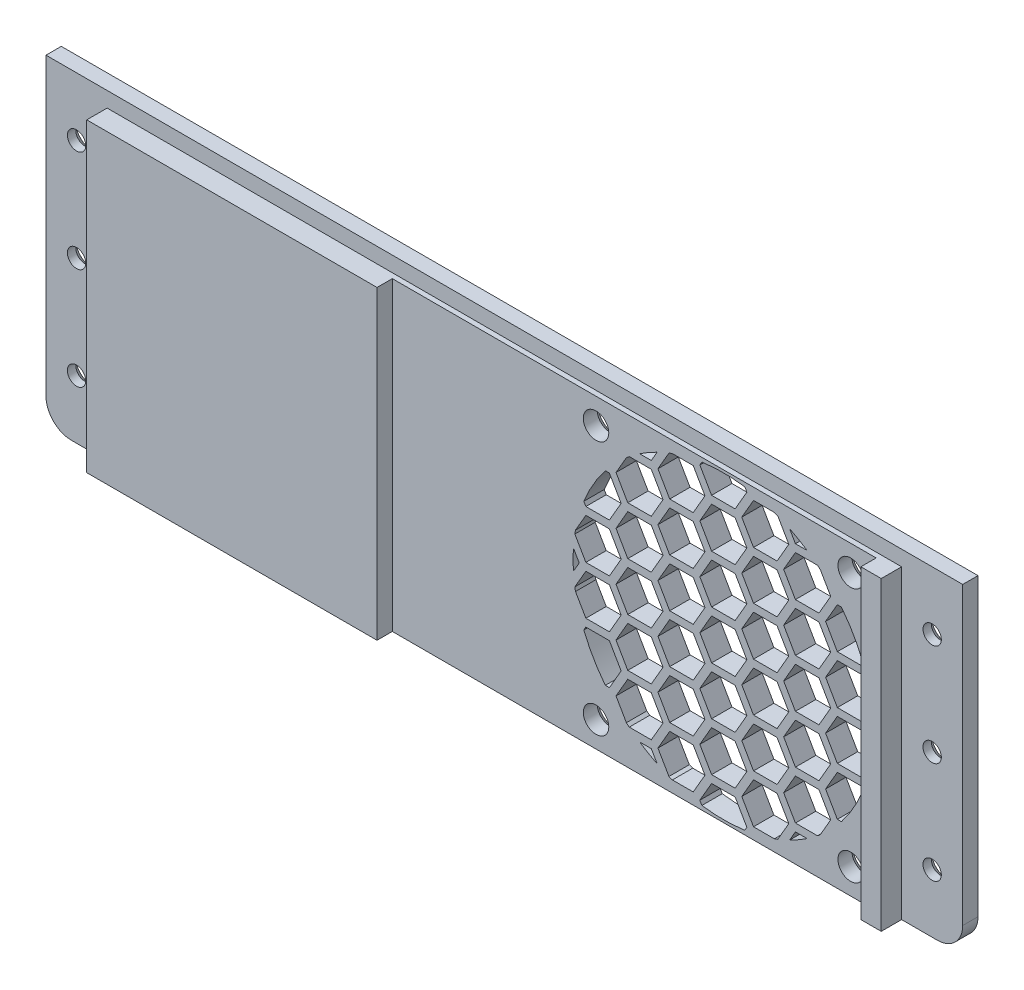
SolidWorks part; units mm, degrees
ref_plane "Front Plane" through (0, 0, 0) normal (0, 0, 1) x (1, 0, 0)
ref_plane "Top Plane" through (0, 0, 0) normal (0, 1, 0) x (1, 0, 0)
ref_plane "Right Plane" through (0, 0, 0) normal (1, 0, 0) x (0, 0, -1)
sketch "Sketch1" plane through (0, 0, 0) normal (0, 0, 1) x (1, 0, 0)
  line L1 (-90, -31.5) -> (90, -31.5)
  line L2 (-90, -31.5) -> (-90, 31.5)
  line L3 (-90, 31.5) -> (90, 31.5)
  line L4 (90, -31.5) -> (90, 31.5)
  line L5 (-90, -31.5) -> (90, 31.5) construction
  line L6 (-90, 31.5) -> (90, -31.5) construction
  point P0 (0, 0)
  dimension "D1" = 180
  dimension "D2" = 63
extrude "Boss-Extrude1" add sketch "Sketch1" along normal blind 3
fillet "Fillet1" radius 5 2 edges at (-90, -31.5, 1.5) (90, -31.5, 1.5)
sketch "Sketch2" plane through (0, 0, 3) normal (0, 0, 1) x (1, 0, 0)
  line L0 (-85, -31.5) -> (85, -31.5) construction
  line L1 (-78, -31.5) -> (78, -31.5)
  line L2 (-78, -31.5) -> (-78, 31.5)
  line L3 (-78, 31.5) -> (78, 31.5)
  line L4 (78, -31.5) -> (78, 31.5)
  line L5 (90, 31.5) -> (-90, 31.5) construction
  dimension "D1" = 12
  dimension "D2" = 12
extrude "Boss-Extrude2" add sketch "Sketch2" along normal blind 4
sketch "Sketch3" plane through (0, 0, 0) normal (0, 0, -1) x (-1, 0, 0)
  line L0 (-90, -26.5) -> (-90, 31.5) construction
  line L2 (90, -26.5) -> (90, 31.5) construction
  point P0 (-84, 20)
  point P2 (-84, -20)
  point P4 (84, 20)
  point P6 (84, -20)
  point P8 (-84, 0)
  point P10 (84, 0)
  dimension "D1" = 6
  dimension "D2" = 20
  dimension "D3" = 20
  dimension "D4" = 6
  dimension "D5" = 20
  dimension "D6" = 20
hole_wizard "CSK for M3 Flat Head Machine Screw1" positions "Sketch3" profile "Sketch4" countersink size "M3" standard "ANSI Metric"
sketch "Sketch4" plane through (84, 20, 0) normal (1, 0, 0) x (0, 1, 0)
  line L0 (0, 0) -> (0, 9.0815)
  line L1 (0, 9.0815) -> (1.8, 8)
  line L2 (1.8, 8) -> (1.8, 1.35)
  line L3 (1.8, 1.35) -> (3.15, 0)
  line L5 (3.15, 0) -> (0, 0)
  line L6 (-1.8, 1.35) -> (-3.15, 0) construction
  line L10 (0, 9.0815) -> (-1.8, 8) construction
  line L11 (0, -6.35) -> (0, 107.95) construction
  dimension "Hole Dia." = 3.6
  dimension "Hole Depth" = 8
  dimension "Near C'Sink Dia." = 6.3
  dimension "Near C'Sink Angle" = 90
  dimension "Drill Angle" = 118
sketch "Sketch9" plane through (0, 0, 7) normal (0, 0, 1) x (1, 0, 0)
  line L0 (-78, -31.5) -> (78, -31.5) construction
  line L1 (14, -31.5) -> (74, -31.5)
  line L2 (14, -31.5) -> (14, 28.5)
  line L3 (14, 28.5) -> (74, 28.5)
  line L4 (74, -31.5) -> (74, 28.5)
  line L5 (14, -31.5) -> (74, 28.5) construction
  line L6 (14, 28.5) -> (74, -31.5) construction
  line L11 (78, -31.5) -> (78, 31.5) construction
  line L13 (69, -26.5) -> (19, -26.5)
  line L14 (69, -26.5) -> (69, 23.5)
  line L15 (69, 23.5) -> (19, 23.5)
  line L16 (19, -26.5) -> (19, 23.5)
  line L17 (69, -26.5) -> (19, 23.5) construction
  line L18 (69, 23.5) -> (19, -26.5) construction
  point P0 (44, -1.5)
  point P10 (44, -1.5)
  dimension "D1" = 60
  dimension "D2" = 60
  dimension "D3" = 4
  dimension "D4" = 50
sketch "Sketch12" plane through (0, 0, 0) normal (0, 0, -1) x (-1, 0, 0)
  point P0 (-19, 23.5)
  point P2 (-19, -26.5)
  point P4 (-69, -26.5)
  point P6 (-69, 23.5)
hole_wizard "CSK for M3 Flat Head Machine Screw3" positions "Sketch12" profile "Sketch14" countersink size "M3" standard "ANSI Metric" end condition through all
sketch "Sketch14" plane through (19, 23.5, 0) normal (1, 0, 0) x (0, 1, 0)
  line L0 (0, 0) -> (0, 7)
  line L1 (0, 7) -> (2.5, 7)
  line L2 (2.5, 7) -> (2.5, 1.25)
  line L3 (2.5, 1.25) -> (3.75, 0)
  line L5 (3.75, 0) -> (0, 0)
  line L6 (-2.5, 1.25) -> (-3.75, 0) construction
  line L11 (0, -6.35) -> (0, 107.95) construction
  dimension "Thru Hole Dia." = 5
  dimension "Thru Hole Depth" = 7
  dimension "Near C'Sink Dia." = 7.5
  dimension "Near C'Sink Angle" = 90
sketch "Sketch15" plane through (0, 0, 7) normal (0, 0, 1) x (1, 0, 0)
  line L0 (-78, -31.5) -> (78, -31.5) construction
  line L1 (74, -31.5) -> (-21, -31.5)
  line L2 (74, -31.5) -> (74, 31.5)
  line L3 (74, 31.5) -> (-21, 31.5)
  line L4 (-21, -31.5) -> (-21, 31.5)
  line L5 (78, 31.5) -> (-78, 31.5) construction
  line L6 (78, -31.5) -> (78, 31.5) construction
  dimension "D1" = 4
  dimension "D2" = 95
extrude "Cut-Extrude3" cut sketch "Sketch15" against normal blind 3
sketch "Sketch16" plane through (0, 0, 0) normal (0, 0, -1) x (-1, 0, 0)
  circle A4 centre (-64, 13.5) radius 3.75
  circle A53 centre (-69, 23.5) radius 3.75 construction
  circle A54 centre (-69, 23.5) radius 3.75
  circle A55 centre (-19, 23.5) radius 3.75 construction
  circle A56 centre (-19, 23.5) radius 3.75
  circle A57 centre (-59, 23.5) radius 3.75
  circle A58 centre (-49, 23.5) radius 3.75
  circle A59 centre (-39, 23.5) radius 3.75
  circle A60 centre (-29, 23.5) radius 3.75
  circle A61 centre (-54, 13.5) radius 3.75
  circle A62 centre (-44, 13.5) radius 3.75
  circle A63 centre (-34, 13.5) radius 3.75
  circle A64 centre (-24, 13.5) radius 3.75
  circle A65 centre (-14, 13.5) radius 3.75
  circle A66 centre (-4, 13.5) radius 3.75
  circle A67 centre (6, 13.5) radius 3.75
  circle A68 centre (-54, -6.5) radius 3.75
  circle A69 centre (-44, -6.5) radius 3.75
  circle A70 centre (-34, -6.5) radius 3.75
  circle A71 centre (-24, -6.5) radius 3.75
  circle A72 centre (-14, -6.5) radius 3.75
  circle A73 centre (-4, -6.5) radius 3.75
  circle A74 centre (6, -6.5) radius 3.75
  circle A75 centre (-64, -6.5) radius 3.75
  circle A76 centre (-59, 23.5) radius 3.75
  circle A77 centre (-49, 23.5) radius 3.75
  circle A78 centre (-39, 23.5) radius 3.75
  circle A79 centre (-29, 23.5) radius 3.75
  circle A80 centre (-19, 23.5) radius 3.75
  circle A81 centre (-9, 23.5) radius 3.75
  circle A82 centre (1, 23.5) radius 3.75
  circle A83 centre (-59, 3.5) radius 3.75
  circle A84 centre (-49, 3.5) radius 3.75
  circle A85 centre (-39, 3.5) radius 3.75
  circle A86 centre (-29, 3.5) radius 3.75
  circle A87 centre (-19, 3.5) radius 3.75
  circle A88 centre (-9, 3.5) radius 3.75
  circle A89 centre (1, 3.5) radius 3.75
  circle A90 centre (-59, -16.5) radius 3.75
  circle A91 centre (-49, -16.5) radius 3.75
  circle A92 centre (-39, -16.5) radius 3.75
  circle A93 centre (-29, -16.5) radius 3.75
  circle A94 centre (-19, -16.5) radius 3.75
  circle A95 centre (-9, -16.5) radius 3.75
  circle A96 centre (1, -16.5) radius 3.75
  circle A97 centre (-69, 3.5) radius 3.75
  circle A98 centre (-69, -16.5) radius 3.75
  dimension "D1" = 5
  dimension "D2" = 10
  dimension "D3" = 5
sketch "Sketch17" plane through (0, 0, 0) normal (0, 0, -1) x (-1, 0, 0)
  circle A0 centre (-44, -1.5) radius 29.5
  dimension "D1" = 59
extrude "Cut-Extrude7" cut sketch "Sketch17" against normal through all
sketch "Sketch18" plane through (0, 31.5, 0) normal (0, 1, 0) x (1, 0, 0)
  line L1 (-90, -3) -> (90, -3)
  line L2 (-90, -3) -> (-90, -11)
  line L3 (-90, -11) -> (90, -11)
  line L4 (90, -3) -> (90, -11)
  dimension "D1" = 8
extrude "Cut-Extrude8" cut sketch "Sketch18" against normal blind 3
sketch "Sketch20" plane through (0, 0, 0) normal (0, 0, -1) x (-1, 0, 0)
  line L0 (-90, -26.5) -> (-90, 31.5) construction
  line L1 (-10, 28) -> (20, 28)
  line L2 (-10, 28) -> (-10, -31)
  line L3 (-10, -31) -> (20, -31)
  line L4 (20, 28) -> (20, -31)
  line L5 (-10, 28) -> (20, -31) construction
  line L6 (-10, -31) -> (20, 28) construction
  circle A0 centre (-44, -1.5) radius 29.5 construction
  point P0 (5, -1.5)
  dimension "D1" = 30
  dimension "D2" = 95
extrude "Cut-Extrude9" cut sketch "Sketch20" against normal through all
sketch "Sketch19" plane through (0, 0, 0) normal (0, 0, -1) x (-1, 0, 0)
  line L0 (-44, -1.5) -> (-35.7728, 3.25) construction
  line L1 (-39.3812, -1.5) -> (-41.6906, 2.5)
  line L2 (-41.6906, 2.5) -> (-46.3094, 2.5)
  line L3 (-46.3094, 2.5) -> (-48.6188, -1.5)
  line L4 (-48.6188, -1.5) -> (-46.3094, -5.5)
  line L5 (-46.3094, -5.5) -> (-41.6906, -5.5)
  line L6 (-41.6906, -5.5) -> (-39.3812, -1.5)
  line L7 (-31.154, 3.25) -> (-33.4634, 7.25)
  line L8 (-33.4634, 7.25) -> (-38.0822, 7.25)
  line L9 (-38.0822, 7.25) -> (-40.3916, 3.25)
  line L10 (-40.3916, 3.25) -> (-38.0822, -0.75)
  line L11 (-38.0822, -0.75) -> (-33.4634, -0.75)
  line L12 (-33.4634, -0.75) -> (-31.154, 3.25)
  line L13 (-44, -1.5) -> (-35.7728, -1.5) construction
  line L14 (-39.3812, -11) -> (-41.6906, -7)
  line L15 (-41.6906, -7) -> (-46.3094, -7)
  line L16 (-46.3094, -7) -> (-48.6188, -11)
  line L17 (-48.6188, -11) -> (-46.3094, -15)
  line L18 (-46.3094, -15) -> (-41.6906, -15)
  line L19 (-41.6906, -15) -> (-39.3812, -11)
  line L20 (-31.154, -6.25) -> (-33.4634, -2.25)
  line L21 (-33.4634, -2.25) -> (-38.0822, -2.25)
  line L22 (-38.0822, -2.25) -> (-40.3916, -6.25)
  line L23 (-40.3916, -6.25) -> (-38.0822, -10.25)
  line L24 (-38.0822, -10.25) -> (-33.4634, -10.25)
  line L25 (-33.4634, -10.25) -> (-31.154, -6.25)
  line L26 (-22.9212, -1.5) -> (-25.2306, 2.5)
  line L27 (-25.2306, 2.5) -> (-29.8494, 2.5)
  line L28 (-29.8494, 2.5) -> (-32.1588, -1.5)
  line L29 (-32.1588, -1.5) -> (-29.8494, -5.5)
  line L30 (-29.8494, -5.5) -> (-25.2306, -5.5)
  line L31 (-25.2306, -5.5) -> (-22.9212, -1.5)
  line L32 (-6.4612, -1.5) -> (-8.7706, 2.5)
  line L33 (-8.7706, 2.5) -> (-13.3894, 2.5)
  line L34 (-13.3894, 2.5) -> (-15.6988, -1.5)
  line L35 (-15.6988, -1.5) -> (-13.3894, -5.5)
  line L36 (-13.3894, -5.5) -> (-8.7706, -5.5)
  line L37 (-8.7706, -5.5) -> (-6.4612, -1.5)
  line L38 (-22.9212, -11) -> (-25.2306, -7)
  line L39 (-25.2306, -7) -> (-29.8494, -7)
  line L40 (-29.8494, -7) -> (-32.1588, -11)
  line L41 (-32.1588, -11) -> (-29.8494, -15)
  line L42 (-29.8494, -15) -> (-25.2306, -15)
  line L43 (-25.2306, -15) -> (-22.9212, -11)
  line L44 (-6.4612, -11) -> (-8.7706, -7)
  line L45 (-8.7706, -7) -> (-13.3894, -7)
  line L46 (-13.3894, -7) -> (-15.6988, -11)
  line L47 (-15.6988, -11) -> (-13.3894, -15)
  line L48 (-13.3894, -15) -> (-8.7706, -15)
  line L49 (-8.7706, -15) -> (-6.4612, -11)
  line L50 (-22.9212, -20.5) -> (-25.2306, -16.5)
  line L51 (-25.2306, -16.5) -> (-29.8494, -16.5)
  line L52 (-29.8494, -16.5) -> (-32.1588, -20.5)
  line L53 (-32.1588, -20.5) -> (-29.8494, -24.5)
  line L54 (-29.8494, -24.5) -> (-25.2306, -24.5)
  line L55 (-25.2306, -24.5) -> (-22.9212, -20.5)
  line L56 (-6.4612, -20.5) -> (-8.7706, -16.5)
  line L57 (-8.7706, -16.5) -> (-13.3894, -16.5)
  line L58 (-13.3894, -16.5) -> (-15.6988, -20.5)
  line L59 (-15.6988, -20.5) -> (-13.3894, -24.5)
  line L60 (-13.3894, -24.5) -> (-8.7706, -24.5)
  line L61 (-8.7706, -24.5) -> (-6.4612, -20.5)
  line L62 (-22.9212, -30) -> (-25.2306, -26)
  line L63 (-25.2306, -26) -> (-29.8494, -26)
  line L64 (-29.8494, -26) -> (-32.1588, -30)
  line L65 (-32.1588, -30) -> (-29.8494, -34)
  line L66 (-29.8494, -34) -> (-25.2306, -34)
  line L67 (-25.2306, -34) -> (-22.9212, -30)
  line L68 (-6.4612, -30) -> (-8.7706, -26)
  line L69 (-8.7706, -26) -> (-13.3894, -26)
  line L70 (-13.3894, -26) -> (-15.6988, -30)
  line L71 (-15.6988, -30) -> (-13.3894, -34)
  line L72 (-13.3894, -34) -> (-8.7706, -34)
  line L73 (-8.7706, -34) -> (-6.4612, -30)
  line L74 (-39.3812, -11) -> (-41.6906, -7)
  line L75 (-41.6906, -7) -> (-46.3094, -7)
  line L76 (-46.3094, -7) -> (-48.6188, -11)
  line L77 (-48.6188, -11) -> (-46.3094, -15)
  line L78 (-46.3094, -15) -> (-41.6906, -15)
  line L79 (-41.6906, -15) -> (-39.3812, -11)
  line L80 (-39.3812, -20.5) -> (-41.6906, -16.5)
  line L81 (-41.6906, -16.5) -> (-46.3094, -16.5)
  line L82 (-46.3094, -16.5) -> (-48.6188, -20.5)
  line L83 (-48.6188, -20.5) -> (-46.3094, -24.5)
  line L84 (-46.3094, -24.5) -> (-41.6906, -24.5)
  line L85 (-41.6906, -24.5) -> (-39.3812, -20.5)
  line L86 (-39.3812, -30) -> (-41.6906, -26)
  line L87 (-41.6906, -26) -> (-46.3094, -26)
  line L88 (-46.3094, -26) -> (-48.6188, -30)
  line L89 (-48.6188, -30) -> (-46.3094, -34)
  line L90 (-46.3094, -34) -> (-41.6906, -34)
  line L91 (-41.6906, -34) -> (-39.3812, -30)
  line L92 (-39.3812, 8) -> (-41.6906, 12)
  line L93 (-41.6906, 12) -> (-46.3094, 12)
  line L94 (-46.3094, 12) -> (-48.6188, 8)
  line L95 (-48.6188, 8) -> (-46.3094, 4)
  line L96 (-46.3094, 4) -> (-41.6906, 4)
  line L97 (-41.6906, 4) -> (-39.3812, 8)
  line L98 (-22.9212, 8) -> (-25.2306, 12)
  line L99 (-25.2306, 12) -> (-29.8494, 12)
  line L100 (-29.8494, 12) -> (-32.1588, 8)
  line L101 (-32.1588, 8) -> (-29.8494, 4)
  line L102 (-29.8494, 4) -> (-25.2306, 4)
  line L103 (-25.2306, 4) -> (-22.9212, 8)
  line L104 (-6.4612, 8) -> (-8.7706, 12)
  line L105 (-8.7706, 12) -> (-13.3894, 12)
  line L106 (-13.3894, 12) -> (-15.6988, 8)
  line L107 (-15.6988, 8) -> (-13.3894, 4)
  line L108 (-13.3894, 4) -> (-8.7706, 4)
  line L109 (-8.7706, 4) -> (-6.4612, 8)
  line L110 (-39.3812, 17.5) -> (-41.6906, 21.5)
  line L111 (-41.6906, 21.5) -> (-46.3094, 21.5)
  line L112 (-46.3094, 21.5) -> (-48.6188, 17.5)
  line L113 (-48.6188, 17.5) -> (-46.3094, 13.5)
  line L114 (-46.3094, 13.5) -> (-41.6906, 13.5)
  line L115 (-41.6906, 13.5) -> (-39.3812, 17.5)
  line L116 (-22.9212, 17.5) -> (-25.2306, 21.5)
  line L117 (-25.2306, 21.5) -> (-29.8494, 21.5)
  line L118 (-29.8494, 21.5) -> (-32.1588, 17.5)
  line L119 (-32.1588, 17.5) -> (-29.8494, 13.5)
  line L120 (-29.8494, 13.5) -> (-25.2306, 13.5)
  line L121 (-25.2306, 13.5) -> (-22.9212, 17.5)
  line L122 (-6.4612, 17.5) -> (-8.7706, 21.5)
  line L123 (-8.7706, 21.5) -> (-13.3894, 21.5)
  line L124 (-13.3894, 21.5) -> (-15.6988, 17.5)
  line L125 (-15.6988, 17.5) -> (-13.3894, 13.5)
  line L126 (-13.3894, 13.5) -> (-8.7706, 13.5)
  line L127 (-8.7706, 13.5) -> (-6.4612, 17.5)
  line L128 (-39.3812, 27) -> (-41.6906, 31)
  line L129 (-41.6906, 31) -> (-46.3094, 31)
  line L130 (-46.3094, 31) -> (-48.6188, 27)
  line L131 (-48.6188, 27) -> (-46.3094, 23)
  line L132 (-46.3094, 23) -> (-41.6906, 23)
  line L133 (-41.6906, 23) -> (-39.3812, 27)
  line L134 (-22.9212, 27) -> (-25.2306, 31)
  line L135 (-25.2306, 31) -> (-29.8494, 31)
  line L136 (-29.8494, 31) -> (-32.1588, 27)
  line L137 (-32.1588, 27) -> (-29.8494, 23)
  line L138 (-29.8494, 23) -> (-25.2306, 23)
  line L139 (-25.2306, 23) -> (-22.9212, 27)
  line L140 (-6.4612, 27) -> (-8.7706, 31)
  line L141 (-8.7706, 31) -> (-13.3894, 31)
  line L142 (-13.3894, 31) -> (-15.6988, 27)
  line L143 (-15.6988, 27) -> (-13.3894, 23)
  line L144 (-13.3894, 23) -> (-8.7706, 23)
  line L145 (-8.7706, 23) -> (-6.4612, 27)
  line L146 (-31.154, 12.75) -> (-33.4634, 16.75)
  line L147 (-33.4634, 16.75) -> (-38.0822, 16.75)
  line L148 (-38.0822, 16.75) -> (-40.3916, 12.75)
  line L149 (-40.3916, 12.75) -> (-38.0822, 8.75)
  line L150 (-38.0822, 8.75) -> (-33.4634, 8.75)
  line L151 (-33.4634, 8.75) -> (-31.154, 12.75)
  line L152 (-31.154, 22.25) -> (-33.4634, 26.25)
  line L153 (-33.4634, 26.25) -> (-38.0822, 26.25)
  line L154 (-38.0822, 26.25) -> (-40.3916, 22.25)
  line L155 (-40.3916, 22.25) -> (-38.0822, 18.25)
  line L156 (-38.0822, 18.25) -> (-33.4634, 18.25)
  line L157 (-33.4634, 18.25) -> (-31.154, 22.25)
  line L158 (-31.154, -15.75) -> (-33.4634, -11.75)
  line L159 (-33.4634, -11.75) -> (-38.0822, -11.75)
  line L160 (-38.0822, -11.75) -> (-40.3916, -15.75)
  line L161 (-40.3916, -15.75) -> (-38.0822, -19.75)
  line L162 (-38.0822, -19.75) -> (-33.4634, -19.75)
  line L163 (-33.4634, -19.75) -> (-31.154, -15.75)
  line L164 (-31.154, -25.25) -> (-33.4634, -21.25)
  line L165 (-33.4634, -21.25) -> (-38.0822, -21.25)
  line L166 (-38.0822, -21.25) -> (-40.3916, -25.25)
  line L167 (-40.3916, -25.25) -> (-38.0822, -29.25)
  line L168 (-38.0822, -29.25) -> (-33.4634, -29.25)
  line L169 (-33.4634, -29.25) -> (-31.154, -25.25)
  line L170 (-31.154, -34.75) -> (-33.4634, -30.75)
  line L171 (-33.4634, -30.75) -> (-38.0822, -30.75)
  line L172 (-38.0822, -30.75) -> (-40.3916, -34.75)
  line L173 (-40.3916, -34.75) -> (-38.0822, -38.75)
  line L174 (-38.0822, -38.75) -> (-33.4634, -38.75)
  line L175 (-33.4634, -38.75) -> (-31.154, -34.75)
  line L176 (-14.694, 22.25) -> (-17.0034, 26.25)
  line L177 (-17.0034, 26.25) -> (-21.6222, 26.25)
  line L178 (-21.6222, 26.25) -> (-23.9316, 22.25)
  line L179 (-23.9316, 22.25) -> (-21.6222, 18.25)
  line L180 (-21.6222, 18.25) -> (-17.0034, 18.25)
  line L181 (-17.0034, 18.25) -> (-14.694, 22.25)
  line L182 (-14.694, 12.75) -> (-17.0034, 16.75)
  line L183 (-17.0034, 16.75) -> (-21.6222, 16.75)
  line L184 (-21.6222, 16.75) -> (-23.9316, 12.75)
  line L185 (-23.9316, 12.75) -> (-21.6222, 8.75)
  line L186 (-21.6222, 8.75) -> (-17.0034, 8.75)
  line L187 (-17.0034, 8.75) -> (-14.694, 12.75)
  line L188 (-14.694, 3.25) -> (-17.0034, 7.25)
  line L189 (-17.0034, 7.25) -> (-21.6222, 7.25)
  line L190 (-21.6222, 7.25) -> (-23.9316, 3.25)
  line L191 (-23.9316, 3.25) -> (-21.6222, -0.75)
  line L192 (-21.6222, -0.75) -> (-17.0034, -0.75)
  line L193 (-17.0034, -0.75) -> (-14.694, 3.25)
  line L194 (-14.694, -6.25) -> (-17.0034, -2.25)
  line L195 (-17.0034, -2.25) -> (-21.6222, -2.25)
  line L196 (-21.6222, -2.25) -> (-23.9316, -6.25)
  line L197 (-23.9316, -6.25) -> (-21.6222, -10.25)
  line L198 (-21.6222, -10.25) -> (-17.0034, -10.25)
  line L199 (-17.0034, -10.25) -> (-14.694, -6.25)
  line L200 (-14.694, -15.75) -> (-17.0034, -11.75)
  line L201 (-17.0034, -11.75) -> (-21.6222, -11.75)
  line L202 (-21.6222, -11.75) -> (-23.9316, -15.75)
  line L203 (-23.9316, -15.75) -> (-21.6222, -19.75)
  line L204 (-21.6222, -19.75) -> (-17.0034, -19.75)
  line L205 (-17.0034, -19.75) -> (-14.694, -15.75)
  line L206 (-14.694, -25.25) -> (-17.0034, -21.25)
  line L207 (-17.0034, -21.25) -> (-21.6222, -21.25)
  line L208 (-21.6222, -21.25) -> (-23.9316, -25.25)
  line L209 (-23.9316, -25.25) -> (-21.6222, -29.25)
  line L210 (-21.6222, -29.25) -> (-17.0034, -29.25)
  line L211 (-17.0034, -29.25) -> (-14.694, -25.25)
  line L212 (-55.8412, 27) -> (-58.1506, 31)
  line L213 (-58.1506, 31) -> (-62.7694, 31)
  line L214 (-62.7694, 31) -> (-65.0788, 27)
  line L215 (-65.0788, 27) -> (-62.7694, 23)
  line L216 (-62.7694, 23) -> (-58.1506, 23)
  line L217 (-58.1506, 23) -> (-55.8412, 27)
  line L218 (-55.8412, 17.5) -> (-58.1506, 21.5)
  line L219 (-58.1506, 21.5) -> (-62.7694, 21.5)
  line L220 (-62.7694, 21.5) -> (-65.0788, 17.5)
  line L221 (-65.0788, 17.5) -> (-62.7694, 13.5)
  line L222 (-62.7694, 13.5) -> (-58.1506, 13.5)
  line L223 (-58.1506, 13.5) -> (-55.8412, 17.5)
  line L224 (-47.614, 22.25) -> (-49.9234, 26.25)
  line L225 (-49.9234, 26.25) -> (-54.5422, 26.25)
  line L226 (-54.5422, 26.25) -> (-56.8516, 22.25)
  line L227 (-56.8516, 22.25) -> (-54.5422, 18.25)
  line L228 (-54.5422, 18.25) -> (-49.9234, 18.25)
  line L229 (-49.9234, 18.25) -> (-47.614, 22.25)
  line L230 (-47.614, 12.75) -> (-49.9234, 16.75)
  line L231 (-49.9234, 16.75) -> (-54.5422, 16.75)
  line L232 (-54.5422, 16.75) -> (-56.8516, 12.75)
  line L233 (-56.8516, 12.75) -> (-54.5422, 8.75)
  line L234 (-54.5422, 8.75) -> (-49.9234, 8.75)
  line L235 (-49.9234, 8.75) -> (-47.614, 12.75)
  line L236 (-55.8412, 8) -> (-58.1506, 12)
  line L237 (-58.1506, 12) -> (-62.7694, 12)
  line L238 (-62.7694, 12) -> (-65.0788, 8)
  line L239 (-65.0788, 8) -> (-62.7694, 4)
  line L240 (-62.7694, 4) -> (-58.1506, 4)
  line L241 (-58.1506, 4) -> (-55.8412, 8)
  line L242 (-47.614, 3.25) -> (-49.9234, 7.25)
  line L243 (-49.9234, 7.25) -> (-54.5422, 7.25)
  line L244 (-54.5422, 7.25) -> (-56.8516, 3.25)
  line L245 (-56.8516, 3.25) -> (-54.5422, -0.75)
  line L246 (-54.5422, -0.75) -> (-49.9234, -0.75)
  line L247 (-49.9234, -0.75) -> (-47.614, 3.25)
  line L248 (-55.8412, -1.5) -> (-58.1506, 2.5)
  line L249 (-58.1506, 2.5) -> (-62.7694, 2.5)
  line L250 (-62.7694, 2.5) -> (-65.0788, -1.5)
  line L251 (-65.0788, -1.5) -> (-62.7694, -5.5)
  line L252 (-62.7694, -5.5) -> (-58.1506, -5.5)
  line L253 (-58.1506, -5.5) -> (-55.8412, -1.5)
  line L254 (-47.614, -6.25) -> (-49.9234, -2.25)
  line L255 (-49.9234, -2.25) -> (-54.5422, -2.25)
  line L256 (-54.5422, -2.25) -> (-56.8516, -6.25)
  line L257 (-56.8516, -6.25) -> (-54.5422, -10.25)
  line L258 (-54.5422, -10.25) -> (-49.9234, -10.25)
  line L259 (-49.9234, -10.25) -> (-47.614, -6.25)
  line L260 (-55.8412, -11) -> (-58.1506, -7)
  line L261 (-58.1506, -7) -> (-62.7694, -7)
  line L262 (-62.7694, -7) -> (-65.0788, -11)
  line L263 (-65.0788, -11) -> (-62.7694, -15)
  line L264 (-62.7694, -15) -> (-58.1506, -15)
  line L265 (-58.1506, -15) -> (-55.8412, -11)
  line L266 (-47.614, -15.75) -> (-49.9234, -11.75)
  line L267 (-49.9234, -11.75) -> (-54.5422, -11.75)
  line L268 (-54.5422, -11.75) -> (-56.8516, -15.75)
  line L269 (-56.8516, -15.75) -> (-54.5422, -19.75)
  line L270 (-54.5422, -19.75) -> (-49.9234, -19.75)
  line L271 (-49.9234, -19.75) -> (-47.614, -15.75)
  line L272 (-55.8412, -20.5) -> (-58.1506, -16.5)
  line L273 (-58.1506, -16.5) -> (-62.7694, -16.5)
  line L274 (-62.7694, -16.5) -> (-65.0788, -20.5)
  line L275 (-65.0788, -20.5) -> (-62.7694, -24.5)
  line L276 (-62.7694, -24.5) -> (-58.1506, -24.5)
  line L277 (-58.1506, -24.5) -> (-55.8412, -20.5)
  line L278 (-47.614, -25.25) -> (-49.9234, -21.25)
  line L279 (-49.9234, -21.25) -> (-54.5422, -21.25)
  line L280 (-54.5422, -21.25) -> (-56.8516, -25.25)
  line L281 (-56.8516, -25.25) -> (-54.5422, -29.25)
  line L282 (-54.5422, -29.25) -> (-49.9234, -29.25)
  line L283 (-49.9234, -29.25) -> (-47.614, -25.25)
  line L284 (-55.8412, -30) -> (-58.1506, -26)
  line L285 (-58.1506, -26) -> (-62.7694, -26)
  line L286 (-62.7694, -26) -> (-65.0788, -30)
  line L287 (-65.0788, -30) -> (-62.7694, -34)
  line L288 (-62.7694, -34) -> (-58.1506, -34)
  line L289 (-58.1506, -34) -> (-55.8412, -30)
  line L290 (-47.614, -34.75) -> (-49.9234, -30.75)
  line L291 (-49.9234, -30.75) -> (-54.5422, -30.75)
  line L292 (-54.5422, -30.75) -> (-56.8516, -34.75)
  line L293 (-56.8516, -34.75) -> (-54.5422, -38.75)
  line L294 (-54.5422, -38.75) -> (-49.9234, -38.75)
  line L295 (-49.9234, -38.75) -> (-47.614, -34.75)
  line L296 (-72.3012, 27) -> (-74.6106, 31)
  line L297 (-74.6106, 31) -> (-79.2294, 31)
  line L298 (-79.2294, 31) -> (-81.5388, 27)
  line L299 (-81.5388, 27) -> (-79.2294, 23)
  line L300 (-79.2294, 23) -> (-74.6106, 23)
  line L301 (-74.6106, 23) -> (-72.3012, 27)
  line L302 (-72.3012, 17.5) -> (-74.6106, 21.5)
  line L303 (-74.6106, 21.5) -> (-79.2294, 21.5)
  line L304 (-79.2294, 21.5) -> (-81.5388, 17.5)
  line L305 (-81.5388, 17.5) -> (-79.2294, 13.5)
  line L306 (-79.2294, 13.5) -> (-74.6106, 13.5)
  line L307 (-74.6106, 13.5) -> (-72.3012, 17.5)
  line L308 (-64.074, 22.25) -> (-66.3834, 26.25)
  line L309 (-66.3834, 26.25) -> (-71.0022, 26.25)
  line L310 (-71.0022, 26.25) -> (-73.3116, 22.25)
  line L311 (-73.3116, 22.25) -> (-71.0022, 18.25)
  line L312 (-71.0022, 18.25) -> (-66.3834, 18.25)
  line L313 (-66.3834, 18.25) -> (-64.074, 22.25)
  line L314 (-64.074, 12.75) -> (-66.3834, 16.75)
  line L315 (-66.3834, 16.75) -> (-71.0022, 16.75)
  line L316 (-71.0022, 16.75) -> (-73.3116, 12.75)
  line L317 (-73.3116, 12.75) -> (-71.0022, 8.75)
  line L318 (-71.0022, 8.75) -> (-66.3834, 8.75)
  line L319 (-66.3834, 8.75) -> (-64.074, 12.75)
  line L320 (-72.3012, 8) -> (-74.6106, 12)
  line L321 (-74.6106, 12) -> (-79.2294, 12)
  line L322 (-79.2294, 12) -> (-81.5388, 8)
  line L323 (-81.5388, 8) -> (-79.2294, 4)
  line L324 (-79.2294, 4) -> (-74.6106, 4)
  line L325 (-74.6106, 4) -> (-72.3012, 8)
  line L326 (-64.074, 3.25) -> (-66.3834, 7.25)
  line L327 (-66.3834, 7.25) -> (-71.0022, 7.25)
  line L328 (-71.0022, 7.25) -> (-73.3116, 3.25)
  line L329 (-73.3116, 3.25) -> (-71.0022, -0.75)
  line L330 (-71.0022, -0.75) -> (-66.3834, -0.75)
  line L331 (-66.3834, -0.75) -> (-64.074, 3.25)
  line L332 (-72.3012, -1.5) -> (-74.6106, 2.5)
  line L333 (-74.6106, 2.5) -> (-79.2294, 2.5)
  line L334 (-79.2294, 2.5) -> (-81.5388, -1.5)
  line L335 (-81.5388, -1.5) -> (-79.2294, -5.5)
  line L336 (-79.2294, -5.5) -> (-74.6106, -5.5)
  line L337 (-74.6106, -5.5) -> (-72.3012, -1.5)
  line L338 (-64.074, -6.25) -> (-66.3834, -2.25)
  line L339 (-66.3834, -2.25) -> (-71.0022, -2.25)
  line L340 (-71.0022, -2.25) -> (-73.3116, -6.25)
  line L341 (-73.3116, -6.25) -> (-71.0022, -10.25)
  line L342 (-71.0022, -10.25) -> (-66.3834, -10.25)
  line L343 (-66.3834, -10.25) -> (-64.074, -6.25)
  line L344 (-72.3012, -11) -> (-74.6106, -7)
  line L345 (-74.6106, -7) -> (-79.2294, -7)
  line L346 (-79.2294, -7) -> (-81.5388, -11)
  line L347 (-81.5388, -11) -> (-79.2294, -15)
  line L348 (-79.2294, -15) -> (-74.6106, -15)
  line L349 (-74.6106, -15) -> (-72.3012, -11)
  line L350 (-64.074, -15.75) -> (-66.3834, -11.75)
  line L351 (-66.3834, -11.75) -> (-71.0022, -11.75)
  line L352 (-71.0022, -11.75) -> (-73.3116, -15.75)
  line L353 (-73.3116, -15.75) -> (-71.0022, -19.75)
  line L354 (-71.0022, -19.75) -> (-66.3834, -19.75)
  line L355 (-66.3834, -19.75) -> (-64.074, -15.75)
  line L356 (-72.3012, -20.5) -> (-74.6106, -16.5)
  line L357 (-74.6106, -16.5) -> (-79.2294, -16.5)
  line L358 (-79.2294, -16.5) -> (-81.5388, -20.5)
  line L359 (-81.5388, -20.5) -> (-79.2294, -24.5)
  line L360 (-79.2294, -24.5) -> (-74.6106, -24.5)
  line L361 (-74.6106, -24.5) -> (-72.3012, -20.5)
  line L362 (-64.074, -25.25) -> (-66.3834, -21.25)
  line L363 (-66.3834, -21.25) -> (-71.0022, -21.25)
  line L364 (-71.0022, -21.25) -> (-73.3116, -25.25)
  line L365 (-73.3116, -25.25) -> (-71.0022, -29.25)
  line L366 (-71.0022, -29.25) -> (-66.3834, -29.25)
  line L367 (-66.3834, -29.25) -> (-64.074, -25.25)
  line L368 (-72.3012, -30) -> (-74.6106, -26)
  line L369 (-74.6106, -26) -> (-79.2294, -26)
  line L370 (-79.2294, -26) -> (-81.5388, -30)
  line L371 (-81.5388, -30) -> (-79.2294, -34)
  line L372 (-79.2294, -34) -> (-74.6106, -34)
  line L373 (-74.6106, -34) -> (-72.3012, -30)
  line L374 (-64.074, -34.75) -> (-66.3834, -30.75)
  line L375 (-66.3834, -30.75) -> (-71.0022, -30.75)
  line L376 (-71.0022, -30.75) -> (-73.3116, -34.75)
  line L377 (-73.3116, -34.75) -> (-71.0022, -38.75)
  line L378 (-71.0022, -38.75) -> (-66.3834, -38.75)
  line L379 (-66.3834, -38.75) -> (-64.074, -34.75)
  line L380 (1.766, 22.25) -> (-0.5434, 26.25)
  line L381 (-0.5434, 26.25) -> (-5.1622, 26.25)
  line L382 (-5.1622, 26.25) -> (-7.4716, 22.25)
  line L383 (-7.4716, 22.25) -> (-5.1622, 18.25)
  line L384 (-5.1622, 18.25) -> (-0.5434, 18.25)
  line L385 (-0.5434, 18.25) -> (1.766, 22.25)
  line L386 (9.9988, 27) -> (7.6894, 31)
  line L387 (7.6894, 31) -> (3.0706, 31)
  line L388 (3.0706, 31) -> (0.7612, 27)
  line L389 (0.7612, 27) -> (3.0706, 23)
  line L390 (3.0706, 23) -> (7.6894, 23)
  line L391 (7.6894, 23) -> (9.9988, 27)
  line L392 (9.9988, 17.5) -> (7.6894, 21.5)
  line L393 (7.6894, 21.5) -> (3.0706, 21.5)
  line L394 (3.0706, 21.5) -> (0.7612, 17.5)
  line L395 (0.7612, 17.5) -> (3.0706, 13.5)
  line L396 (3.0706, 13.5) -> (7.6894, 13.5)
  line L397 (7.6894, 13.5) -> (9.9988, 17.5)
  line L398 (1.766, 12.75) -> (-0.5434, 16.75)
  line L399 (-0.5434, 16.75) -> (-5.1622, 16.75)
  line L400 (-5.1622, 16.75) -> (-7.4716, 12.75)
  line L401 (-7.4716, 12.75) -> (-5.1622, 8.75)
  line L402 (-5.1622, 8.75) -> (-0.5434, 8.75)
  line L403 (-0.5434, 8.75) -> (1.766, 12.75)
  line L404 (9.9988, 8) -> (7.6894, 12)
  line L405 (7.6894, 12) -> (3.0706, 12)
  line L406 (3.0706, 12) -> (0.7612, 8)
  line L407 (0.7612, 8) -> (3.0706, 4)
  line L408 (3.0706, 4) -> (7.6894, 4)
  line L409 (7.6894, 4) -> (9.9988, 8)
  line L410 (1.766, 3.25) -> (-0.5434, 7.25)
  line L411 (-0.5434, 7.25) -> (-5.1622, 7.25)
  line L412 (-5.1622, 7.25) -> (-7.4716, 3.25)
  line L413 (-7.4716, 3.25) -> (-5.1622, -0.75)
  line L414 (-5.1622, -0.75) -> (-0.5434, -0.75)
  line L415 (-0.5434, -0.75) -> (1.766, 3.25)
  line L416 (9.9988, -1.5) -> (7.6894, 2.5)
  line L417 (7.6894, 2.5) -> (3.0706, 2.5)
  line L418 (3.0706, 2.5) -> (0.7612, -1.5)
  line L419 (0.7612, -1.5) -> (3.0706, -5.5)
  line L420 (3.0706, -5.5) -> (7.6894, -5.5)
  line L421 (7.6894, -5.5) -> (9.9988, -1.5)
  line L422 (1.766, -6.25) -> (-0.5434, -2.25)
  line L423 (-0.5434, -2.25) -> (-5.1622, -2.25)
  line L424 (-5.1622, -2.25) -> (-7.4716, -6.25)
  line L425 (-7.4716, -6.25) -> (-5.1622, -10.25)
  line L426 (-5.1622, -10.25) -> (-0.5434, -10.25)
  line L427 (-0.5434, -10.25) -> (1.766, -6.25)
  line L428 (9.9988, -11) -> (7.6894, -7)
  line L429 (7.6894, -7) -> (3.0706, -7)
  line L430 (3.0706, -7) -> (0.7612, -11)
  line L431 (0.7612, -11) -> (3.0706, -15)
  line L432 (3.0706, -15) -> (7.6894, -15)
  line L433 (7.6894, -15) -> (9.9988, -11)
  line L434 (1.766, -15.75) -> (-0.5434, -11.75)
  line L435 (-0.5434, -11.75) -> (-5.1622, -11.75)
  line L436 (-5.1622, -11.75) -> (-7.4716, -15.75)
  line L437 (-7.4716, -15.75) -> (-5.1622, -19.75)
  line L438 (-5.1622, -19.75) -> (-0.5434, -19.75)
  line L439 (-0.5434, -19.75) -> (1.766, -15.75)
  line L440 (9.9988, -20.5) -> (7.6894, -16.5)
  line L441 (7.6894, -16.5) -> (3.0706, -16.5)
  line L442 (3.0706, -16.5) -> (0.7612, -20.5)
  line L443 (0.7612, -20.5) -> (3.0706, -24.5)
  line L444 (3.0706, -24.5) -> (7.6894, -24.5)
  line L445 (7.6894, -24.5) -> (9.9988, -20.5)
  line L446 (1.766, -25.25) -> (-0.5434, -21.25)
  line L447 (-0.5434, -21.25) -> (-5.1622, -21.25)
  line L448 (-5.1622, -21.25) -> (-7.4716, -25.25)
  line L449 (-7.4716, -25.25) -> (-5.1622, -29.25)
  line L450 (-5.1622, -29.25) -> (-0.5434, -29.25)
  line L451 (-0.5434, -29.25) -> (1.766, -25.25)
  line L452 (9.9988, -30) -> (7.6894, -26)
  line L453 (7.6894, -26) -> (3.0706, -26)
  line L454 (3.0706, -26) -> (0.7612, -30)
  line L455 (0.7612, -30) -> (3.0706, -34)
  line L456 (3.0706, -34) -> (7.6894, -34)
  line L457 (7.6894, -34) -> (9.9988, -30)
  line L458 (18.226, 22.25) -> (15.9166, 26.25)
  line L459 (15.9166, 26.25) -> (11.2978, 26.25)
  line L460 (11.2978, 26.25) -> (8.9884, 22.25)
  line L461 (8.9884, 22.25) -> (11.2978, 18.25)
  line L462 (11.2978, 18.25) -> (15.9166, 18.25)
  line L463 (15.9166, 18.25) -> (18.226, 22.25)
  line L464 (26.4588, 27) -> (24.1494, 31)
  line L465 (24.1494, 31) -> (19.5306, 31)
  line L466 (19.5306, 31) -> (17.2212, 27)
  line L467 (17.2212, 27) -> (19.5306, 23)
  line L468 (19.5306, 23) -> (24.1494, 23)
  line L469 (24.1494, 23) -> (26.4588, 27)
  line L470 (26.4588, 17.5) -> (24.1494, 21.5)
  line L471 (24.1494, 21.5) -> (19.5306, 21.5)
  line L472 (19.5306, 21.5) -> (17.2212, 17.5)
  line L473 (17.2212, 17.5) -> (19.5306, 13.5)
  line L474 (19.5306, 13.5) -> (24.1494, 13.5)
  line L475 (24.1494, 13.5) -> (26.4588, 17.5)
  line L476 (18.226, 12.75) -> (15.9166, 16.75)
  line L477 (15.9166, 16.75) -> (11.2978, 16.75)
  line L478 (11.2978, 16.75) -> (8.9884, 12.75)
  line L479 (8.9884, 12.75) -> (11.2978, 8.75)
  line L480 (11.2978, 8.75) -> (15.9166, 8.75)
  line L481 (15.9166, 8.75) -> (18.226, 12.75)
  line L482 (26.4588, 8) -> (24.1494, 12)
  line L483 (24.1494, 12) -> (19.5306, 12)
  line L484 (19.5306, 12) -> (17.2212, 8)
  line L485 (17.2212, 8) -> (19.5306, 4)
  line L486 (19.5306, 4) -> (24.1494, 4)
  line L487 (24.1494, 4) -> (26.4588, 8)
  line L488 (18.226, 3.25) -> (15.9166, 7.25)
  line L489 (15.9166, 7.25) -> (11.2978, 7.25)
  line L490 (11.2978, 7.25) -> (8.9884, 3.25)
  line L491 (8.9884, 3.25) -> (11.2978, -0.75)
  line L492 (11.2978, -0.75) -> (15.9166, -0.75)
  line L493 (15.9166, -0.75) -> (18.226, 3.25)
  line L494 (26.4588, -1.5) -> (24.1494, 2.5)
  line L495 (24.1494, 2.5) -> (19.5306, 2.5)
  line L496 (19.5306, 2.5) -> (17.2212, -1.5)
  line L497 (17.2212, -1.5) -> (19.5306, -5.5)
  line L498 (19.5306, -5.5) -> (24.1494, -5.5)
  line L499 (24.1494, -5.5) -> (26.4588, -1.5)
  line L500 (18.226, -6.25) -> (15.9166, -2.25)
  line L501 (15.9166, -2.25) -> (11.2978, -2.25)
  line L502 (11.2978, -2.25) -> (8.9884, -6.25)
  line L503 (8.9884, -6.25) -> (11.2978, -10.25)
  line L504 (11.2978, -10.25) -> (15.9166, -10.25)
  line L505 (15.9166, -10.25) -> (18.226, -6.25)
  line L506 (26.4588, -11) -> (24.1494, -7)
  line L507 (24.1494, -7) -> (19.5306, -7)
  line L508 (19.5306, -7) -> (17.2212, -11)
  line L509 (17.2212, -11) -> (19.5306, -15)
  line L510 (19.5306, -15) -> (24.1494, -15)
  line L511 (24.1494, -15) -> (26.4588, -11)
  line L512 (18.226, -15.75) -> (15.9166, -11.75)
  line L513 (15.9166, -11.75) -> (11.2978, -11.75)
  line L514 (11.2978, -11.75) -> (8.9884, -15.75)
  line L515 (8.9884, -15.75) -> (11.2978, -19.75)
  line L516 (11.2978, -19.75) -> (15.9166, -19.75)
  line L517 (15.9166, -19.75) -> (18.226, -15.75)
  line L518 (26.4588, -20.5) -> (24.1494, -16.5)
  line L519 (24.1494, -16.5) -> (19.5306, -16.5)
  line L520 (19.5306, -16.5) -> (17.2212, -20.5)
  line L521 (17.2212, -20.5) -> (19.5306, -24.5)
  line L522 (19.5306, -24.5) -> (24.1494, -24.5)
  line L523 (24.1494, -24.5) -> (26.4588, -20.5)
  line L524 (18.226, -25.25) -> (15.9166, -21.25)
  line L525 (15.9166, -21.25) -> (11.2978, -21.25)
  line L526 (11.2978, -21.25) -> (8.9884, -25.25)
  line L527 (8.9884, -25.25) -> (11.2978, -29.25)
  line L528 (11.2978, -29.25) -> (15.9166, -29.25)
  line L529 (15.9166, -29.25) -> (18.226, -25.25)
  line L530 (26.4588, -30) -> (24.1494, -26)
  line L531 (24.1494, -26) -> (19.5306, -26)
  line L532 (19.5306, -26) -> (17.2212, -30)
  line L533 (17.2212, -30) -> (19.5306, -34)
  line L534 (19.5306, -34) -> (24.1494, -34)
  line L535 (24.1494, -34) -> (26.4588, -30)
  line L536 (-10, -31) -> (20, -31) construction
  line L537 (20, -31) -> (20, 28) construction
  line L538 (-10, 28) -> (-10, -31) construction
  line L539 (20, 28) -> (-10, 28) construction
  line L540 (-10, -31) -> (20, -31)
  line L541 (20, -31) -> (20, 28)
  line L542 (-10, 28) -> (-10, -31)
  line L543 (20, 28) -> (-10, 28)
  circle A0 centre (-44, -1.5) radius 29.5 construction
  circle A1 centre (-44, -1.5) radius 29.5
  circle A2 centre (-44, -1.5) radius 4 construction
  circle A3 centre (-35.7728, 3.25) radius 4 construction
  circle M119 centre (-44, -1.5) radius 29.5
  line M415 (20, 28) -> (20, -31)
  line M417 (-10, -31) -> (-10, 28)
  line M418 (-10, 28) -> (20, 28)
  dimension "D1" = 4
  dimension "D2" = 1.5
  dimension "D3" = 30
  dimension "D4" = 2
  dimension "D5" = 3
  dimension "D6" = 4
  dimension "D9" = 4
  dimension "D7" = 3
  dimension "D8" = 4
  dimension "D10" = 2
extrude "Boss-Extrude3" add sketch "Sketch19" against normal up to surface (4 mm away) contours L355 L354 L275 L274 L273 L272 L277 L276 L285 L284 L281 L280 L279 L278 L283 L282 L89 L88 L87 L86 L91 L168 L167 L166 L165 L164 L169 L64 L63 L54 L53 L52 L51 L50 L55 L204 L203 L202 L201 L200 L199 L198 M119 | L533 L532 L531 L522 L521 L520 L519 L510 L509 L508 L507 L498 L497 L496 L495 L486 L485 L484 L483 L474 L473 L472 L471 L468 L467 L466 L386 L391 L390 L389 L388 L140 L145 L144 L123 L122 L127 L126 L105 L104 L109 M415 M418 M417 region at (7.0427, 0.8309, 0) region at (15.8502, -0.1038, 0) up to face at (-5, -1.5, 4)
extrude "Boss-Extrude4" add sketch "Sketch20<2>" against normal up to surface (4 mm away) up to face at (-18.9101, -28.8, 4)
sketch "Sketch20<2>" plane through (0, 0, 0) normal (0, 0, -1) x (-1, 0, 0) same geometry as "Sketch20"
